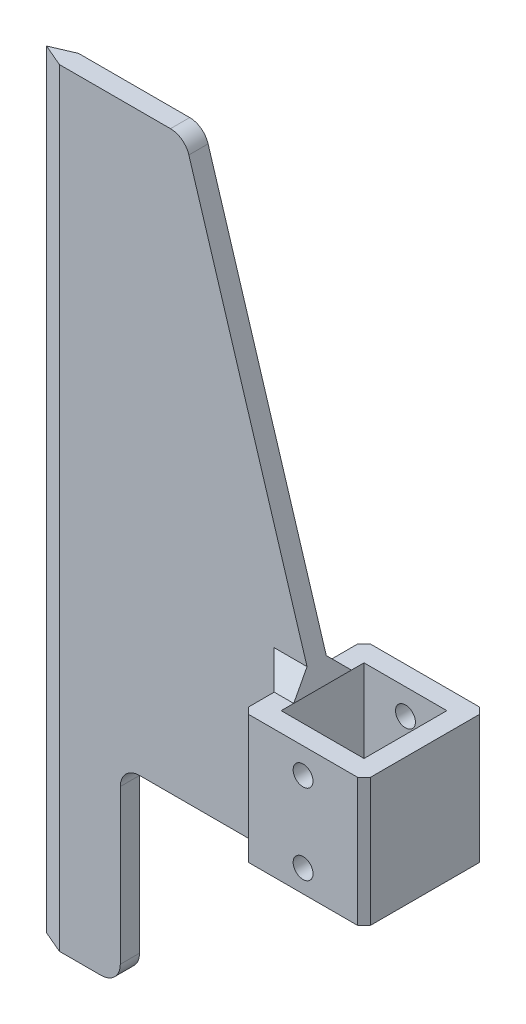
SolidWorks part; units mm, degrees
ref_plane "Front Plane" through (0, 0, 0) normal (0, 0, 1) x (1, 0, 0)
ref_plane "Top Plane" through (0, 0, 0) normal (0, 1, 0) x (1, 0, 0)
ref_plane "Right Plane" through (0, 0, 0) normal (1, 0, 0) x (0, 0, -1)
sketch "Sketch1" plane through (0, 0, 0) normal (0, 1, 0) x (1, 0, 0)
  line L1 (0, 0) -> (19, 0)
  line L2 (0, 0) -> (0, 19)
  line L3 (0, 19) -> (19, 19)
  line L4 (19, 0) -> (19, 19)
  line L5 (3.44, 15.56) -> (15.56, 15.56)
  line L6 (3.44, 15.56) -> (3.44, 3.44)
  line L7 (3.44, 3.44) -> (15.56, 3.44)
  line L8 (15.56, 15.56) -> (15.56, 3.44)
  dimension "D1" = 19
  dimension "D2" = 19
  dimension "3.46" = 3.44
  dimension "D4" = 3.44
  dimension "D5" = 3.44
  dimension "D6" = 3.44
extrude "Boss-Extrude1" add sketch "Sketch1" along normal blind 20
sketch "Sketch2" plane through (0, 0, 0) normal (0, 0, 1) x (1, 0, 0)
  line L0 (9.5, 20) -> (9.5, 0) construction
  line L1 (0, 20) -> (19, 20) construction
  line L2 (0, 0) -> (19, 0) construction
  line L3 (19, 20) -> (19, 0) construction
  circle A0 centre (9.5, 16) radius 1.55
  circle A1 centre (9.5, 3.5) radius 1.55
  dimension "D1" = 12.5
  dimension "D2" = 3.5
  dimension "D3" = 3.1
  dimension "D4" = 3.1
extrude "Cut-Extrude1" cut sketch "Sketch2" against normal blind 22
ref_plane "Plane1" through (0, 0, 0) normal (1, 0, 0) x (0, 0, -1)
sketch "Sketch3" plane through (0, 0, 0) normal (0, -1, 0) x (1, 0, 0)
  line L0 (3.44, -15.56) -> (3.44, -3.44) construction
  line L1 (3.04, -3.04) -> (15.96, -3.04)
  line L2 (3.04, -3.04) -> (3.04, -15.96)
  line L3 (3.04, -15.96) -> (15.96, -15.96)
  line L4 (15.96, -3.04) -> (15.96, -15.96)
  line L5 (3.44, -3.44) -> (15.56, -3.44) construction
  line L6 (15.56, -3.44) -> (15.56, -15.56) construction
  line L7 (15.56, -15.56) -> (3.44, -15.56) construction
  dimension "D1" = 0.4
  dimension "D2" = 0.4
  dimension "D3" = 0.4
  dimension "D4" = 0.4
extrude "Cut-Extrude2" cut sketch "Sketch3" against normal blind 20
sketch "Sketch4" plane through (0, 0, 0) normal (-1, 0, 0) x (0, 0, 1)
  line L0 (-9.5, 20) -> (-9.5, 0) construction
  line L1 (-19, 20) -> (0, 20) construction
  line L2 (-19, 0) -> (0, 0) construction
  line L3 (-11, -4.7465) -> (-8, -4.7465)
  line L5 (-11, -4.7465) -> (-11, 70)
  line L7 (-8, -4.7465) -> (-8, 70)
  line L11 (-11, 70) -> (-11, -4.7465)
  line L13 (-8, 70) -> (-8, -4.7465)
  line L15 (-8, 70) -> (-8, 85)
  line L16 (-8, 85) -> (-11, 85)
  line L17 (-11, 70) -> (-11, 85)
  line M9 (-19, 0) -> (0, 0)
  line M11 (0, 20) -> (-19, 20)
  dimension "D1" = 3
  dimension "D2" = 15
extrude "Boss-Extrude2" add sketch "Sketch4" along normal blind 40 and the other way blind 3.04 contours L7 L5 M11 | L0 L5 M11 M9 | L0 L7 M11 M9 | L5 L7 M9 region at (0, 10, -8.75) region at (0, 52.5, -9.5) region at (0, 10, -10.25) region at (0, -2.3732, -9.5)
sketch "Sketch5" plane through (0, 0, -8) normal (0, 0, 1) x (1, 0, 0)
  line L0 (-16.96, 85) -> (3.04, 20)
  line L1 (3.04, 85) -> (-40, 85) construction
  line L2 (3.04, 20) -> (3.04, 85)
  line L3 (3.04, 85) -> (-16.96, 85)
  dimension "D1" = 20
extrude "Cut-Extrude3" cut sketch "Sketch5" against normal blind 40
sketch "Sketch7" plane through (0, -4.7465, 0) normal (0, -1, 0) x (1, 0, 0)
  line L0 (3.04, -11) -> (-40, -11) construction
  line L1 (-40, -8) -> (-27, -8)
  line L2 (-40, -8) -> (-40, -11)
  line L3 (-40, -11) -> (-27, -11)
  line L4 (-27, -8) -> (-27, -11)
  dimension "D1" = 13
extrude "Boss-Extrude3" add sketch "Sketch7" along normal blind 30
sketch "Sketch8" plane through (0, -34.7465, 0) normal (0, -1, 0) x (1, 0, 0)
  line L0 (-40, -9.5) -> (-36.5, -8)
  line L1 (-40, -8) -> (-40, -11) construction
  line L2 (-27, -8) -> (-40, -8) construction
  line L3 (-40, -9.5) -> (-36.5, -11)
  line L4 (-40, -11) -> (-27, -11) construction
  line L5 (-36.5, -11) -> (-40, -11)
  line L6 (-40, -11) -> (-40, -8)
  line L7 (-40, -8) -> (-36.5, -8)
  line M1 (-40, -8) -> (-40, -11)
  line M2 (-40, -11) -> (-27, -11)
  line M4 (-27, -8) -> (-40, -8)
  dimension "D1" = 3.5
extrude "Cut-Extrude4" cut sketch "Sketch8" against normal blind 129 contours L0 M1 M4 | L3 M1 M2 region at (-38.8333, -34.7465, -8.5) region at (-38.8333, -34.7465, -10.5)
fillet "Fillet2" radius 3 1 edges at (-27, -4.7465, -9.5)
fillet "Fillet3" radius 3 1 edges at (-27, -34.7465, -9.5)
fillet "Fillet4" radius 3 1 edges at (-16.96, 85, -9.5)
fillet "Fillet5" radius 4.75 2 edges at (1.52, 0, -8) (1.52, 0, -11) profile chamfer
fillet "Fillet6" radius 3 2 edges at (1.52, 20, -11) (1.52, 20, -8) profile chamfer
fillet "Fillet7" radius 3 2 edges at (0, 9.1268, -11) (0, 9.1268, -8) profile chamfer
fillet "Fillet8" radius 1 4 edges at (0, 10, 0) (0, 10, -19) (19, 10, 0) (19, 10, -19) profile chamfer
